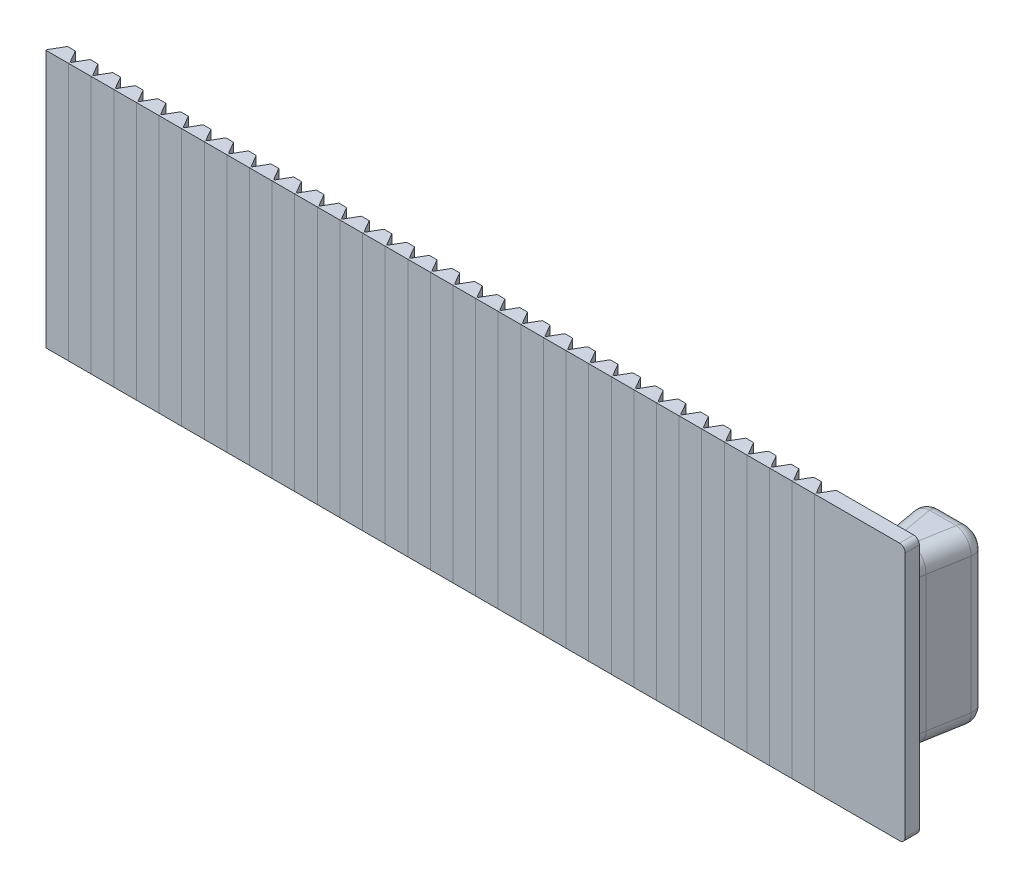
SolidWorks part; units mm, degrees
ref_plane "前视基准面" through (0, 0, 0) normal (0, 0, 1) x (1, 0, 0)
ref_plane "上视基准面" through (0, 0, 0) normal (0, 1, 0) x (1, 0, 0)
ref_plane "右视基准面" through (0, 0, 0) normal (1, 0, 0) x (0, 0, -1)
other "Configuration Table"
sketch "草图1" plane through (0, 0, 0) normal (0, 1, 0) x (1, 0, 0)
  line L0 (0, 130) -> (0, 0) construction
  line L1 (0, 0) -> (185, 0) construction
  line L2 (185, 0) -> (181, 0)
  line L6 (181, 0) -> (181, 0.4)
  line L7 (181, 0.4) -> (181.1, 0.4)
  line L8 (181.1, 0.4) -> (182.3124, 2.5)
  line L9 (182.3124, 2.5) -> (183.6876, 2.5)
  line L10 (183.6876, 2.5) -> (184.9, 0.4)
  line L11 (184.9, 0.4) -> (185, 0.4)
  line L12 (185, 0.4) -> (185, 0)
  dimension "D1" = 130
  dimension "D2" = 185
  dimension "D3" = 0.4
  dimension "D4" = 4
  dimension "D5" = 0.1
  dimension "D6" = 60
  dimension "D7" = 2.5
extrude "凸台-拉伸1" add sketch "草图1" along normal mid plane 45.6
pattern_linear "阵列(线性)1" count 38 spacing 4 along (-1, 0, 0) of bodies 106
sketch "草图2" plane through (0, 0, 0) normal (0, 0, 1) x (1, 0, 0)
  line L0 (169, -22.8) -> (173, -22.8) construction
  line L1 (185, 22.8) -> (171, 22.8)
  line L2 (185, 22.8) -> (185, -22.8)
  line L3 (185, -22.8) -> (171, -22.8)
  line L4 (171, 22.8) -> (171, -22.8)
  dimension "D1" = 14
extrude "凸台-拉伸2" add sketch "草图2" against normal up to surface (2.5 mm away) up to face at (179, 0, -2.5)
sketch "草图3" plane through (0, 0, 0) normal (0, 0, 1) x (1, 0, 0)
  line L0 (177, 10) -> (177, -10) construction
  line L1 (177, 0) -> (185, 0) construction
  line L2 (185, 22.8) -> (185, -22.8) construction
  circle A0 centre (177, -10) radius 1.65
  circle A1 centre (177, 10) radius 1.65
  dimension "D3" = 3.3
  dimension "D1" = 20
  dimension "D2" = 8
extrude "切除-拉伸1" [suppressed] cut sketch "草图3" against normal through all
fillet "圆角2" radius 1 2 edges at (185, -22.8, -1.25) (185, 22.8, -1.25)
chamfer "倒角2" [suppressed] distance 0.2 angle 45
sketch "草图4" plane through (0, 0, 0) normal (0, 1, 0) x (1, 0, 0)
  line L0 (172.1746, 2.5) -> (172.1746, 7.5)
  line L1 (184, 2.5) -> (170.3124, 2.5) construction
  line L2 (172.1746, 7.5) -> (170.4113, 17.5)
  line L3 (170.4113, 17.5) -> (181.9379, 17.5)
  line L4 (181.9379, 17.5) -> (180.1746, 7.5)
  line L5 (180.1746, 7.5) -> (180.1746, 2.5)
  line L6 (180.1746, 2.5) -> (172.1746, 2.5)
  line L7 (176.1746, 2.5) -> (176.1746, 17.5) construction
  dimension "D1" = 8
  dimension "D2" = 10
  dimension "D3" = 15
  dimension "D4" = 5
extrude "凸台-拉伸3" add sketch "草图4" along normal mid plane 30
fillet "圆角3" radius 10 2 edges at (172.1746, 0, -7.5) (180.1746, 0, -7.5)
fillet "圆角4" radius 3 12 edges at (171.217, -15, -12.9308) (172.1365, -15, -7.4967) (181.1322, -15, -12.9308) (180.2126, -15, -7.4967) (181.1322, 15, -12.9308) (180.2126, 15, -7.4967) (171.217, 15, -12.9308) (172.1365, 15, -7.4967) (172.1746, -15, -4.5626) (180.1746, -15, -4.5626) (180.1746, 15, -4.5626) (172.1746, 15, -4.5626)
fillet "圆角5" radius 2 8 edges at (181.0456, 14.1213, -17.5) (176.1746, 15, -17.5) (171.3036, 14.1213, -17.5) (170.4113, 0, -17.5) (171.3036, -14.1213, -17.5) (176.1746, -15, -17.5) (181.0456, -14.1213, -17.5) (181.9379, 0, -17.5)
